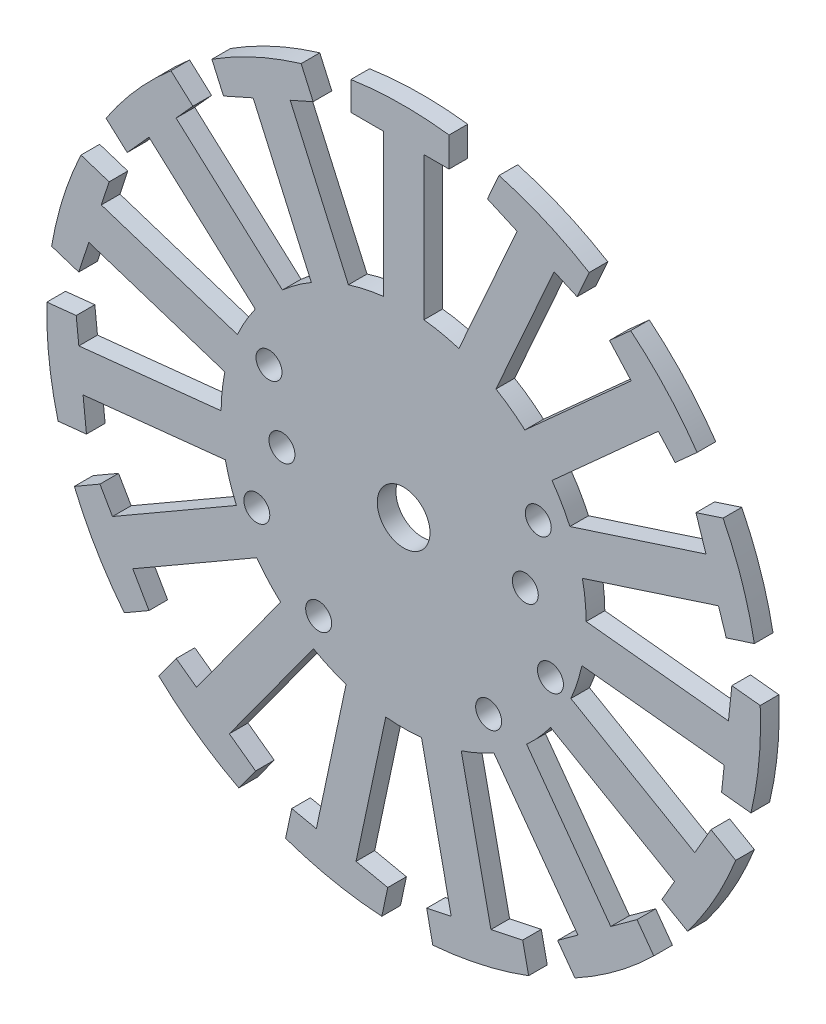
SolidWorks part; units mm, degrees
material "AISI 1010 鋼, 熱間圧延棒"
ref_plane "正面" through (0, 0, 0) normal (0, 0, 1) x (1, 0, 0)
ref_plane "平面" through (0, 0, 0) normal (0, 1, 0) x (1, 0, 0)
ref_plane "右側面" through (0, 0, 0) normal (1, 0, 0) x (0, 0, -1)
sketch "ｽｹｯﾁ1" plane through (0, 0, 0) normal (0, 0, 1) x (1, 0, 0)
  line L0 (0, 0) -> (0, 40)
  line L1 (0, 0) -> (-2.5, 0)
  line L2 (-2.5, 0) -> (-2.5, 40)
  line L3 (0, 0) -> (2.5, 0)
  line L4 (2.5, 0) -> (2.5, 40)
  line L6 (-2.5, 40) -> (-6.5, 40)
  line L7 (2.5, 40) -> (5.6, 40)
  line L8 (5.6, 40) -> (5.6, 43.6422)
  line L9 (-6.5, 40) -> (-6.5, 43.5172)
  arc A1 (5.6, 43.6422) -> (-6.5, 43.5172) centre (0, 0) ccw
  circle A2 centre (0, 0) radius 22.5
  dimension "D2" = 88
  dimension "D3" = 45
  dimension "D4" = 2.5
  dimension "D5" = 2.5
  dimension "D7" = 6.5
  dimension "D8" = 5.6
extrude "ﾎﾞｽ - 押し出し2" add sketch "ｽｹｯﾁ1" along normal blind 2.3 contours L2 A2 L4 L3 L1 | L1 L2 L6 L9 A1 L8 L7 L4 L3 region at (0, -0.8527, 0)
pattern_circular "円形ﾊﾟﾀｰﾝ2" count 15 over 360 about axis through (0, 0, 2.3) along (0, 0, 1) of "ﾎﾞｽ - 押し出し2"
sketch "ｽｹｯﾁ3" plane through (0, 0, 2.3) normal (0, 0, 1) x (1, 0, 0)
  circle A0 centre (0, 0) radius 3.25
  dimension "D1" = 6.5
extrude "ｶｯﾄ - 押し出し2" cut sketch "ｽｹｯﾁ3" against normal blind 3.2
sketch "ｽｹｯﾁ5" plane through (0, 0, 2.3) normal (0, 0, 1) x (1, 0, 0)
  line L0 (-15, 0) -> (15, 0)
  line L1 (0, 0) -> (0, -15.75)
  line L2 (-10.4775, -15.75) -> (10.4775, -15.75)
  circle A0 centre (-15, 0) radius 1.6
  circle A1 centre (15, 0) radius 1.6
  circle A2 centre (10.4775, -15.75) radius 1.6
  circle A3 centre (-10.4775, -15.75) radius 1.6
  point P5 (0, 0)
  point P11 (0, -15.75)
  point P17 (0, 17)
  dimension "D1" = 3.2
  dimension "D4" = 3.2
  dimension "D5" = 3.2
  dimension "D2" = 15.75
  dimension "D3" = 10.4775
extrude "ｶｯﾄ - 押し出し3" cut sketch "ｽｹｯﾁ5" against normal blind 10 contours A0 | A1 | A3 | A2
sketch "ｽｹｯﾁ6" plane through (0, 0, 2.3) normal (0, 0, 1) x (1, 0, 0)
  line L0 (0, 0) -> (-16.6, 0)
  line L1 (-16.6, 0) -> (-16.6, 8)
  line L2 (0, 0) -> (0, 11.5739)
  line L3 (-16.6, 0) -> (-18.1, 0)
  line L4 (-18.1, 0) -> (-18.1, -8)
  circle A0 centre (-15, 0) radius 1.6 construction
  circle A1 centre (-16.6, 8) radius 1.6
  circle A5 centre (-18.1, -8) radius 1.6
  circle A6 centre (18.1, -8) radius 1.6
  circle A7 centre (16.6, 8) radius 1.6
  dimension "D2" = 3.2
  dimension "D5" = 3.2
  dimension "D1" = 8
  dimension "D3" = 1.5
  dimension "D4" = 8
  dimension "D6" = 16.6
extrude "ｶｯﾄ - 押し出し4" cut sketch "ｽｹｯﾁ6" against normal blind 10 contours A1 | A5 | A6 | A7
